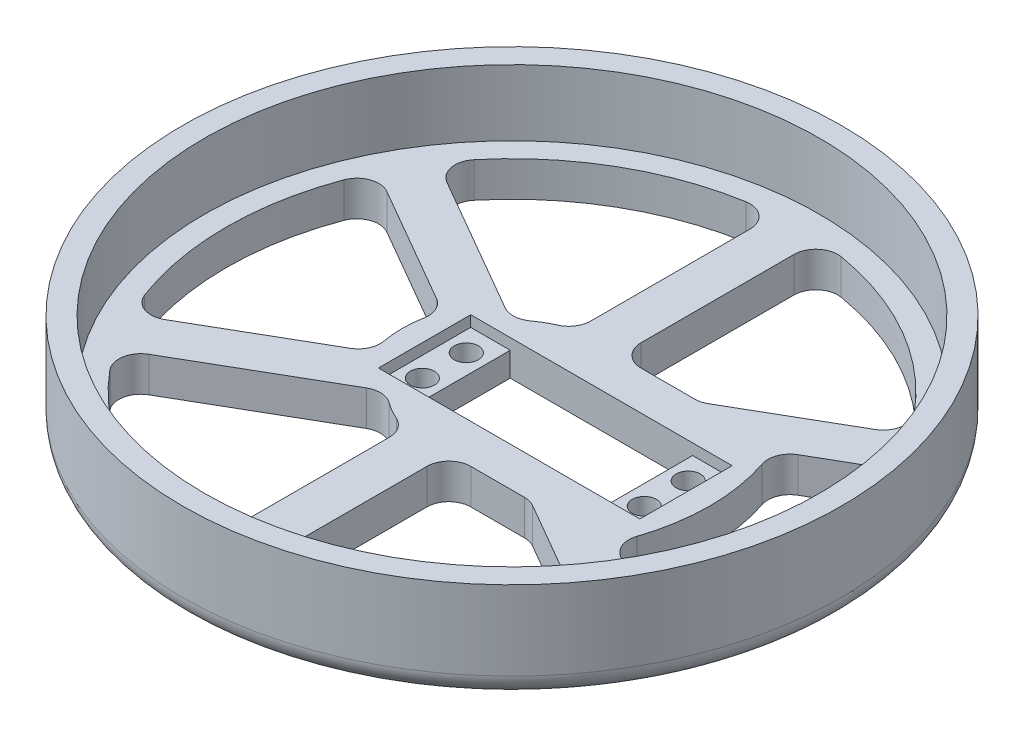
SolidWorks part; units mm, degrees
ref_plane "Front Plane" through (0, 0, 0) normal (0, 0, 1) x (1, 0, 0)
ref_plane "Top Plane" through (0, 0, 0) normal (0, 1, 0) x (1, 0, 0)
ref_plane "Right Plane" through (0, 0, 0) normal (1, 0, 0) x (0, 0, -1)
sketch "Sketch1" plane through (0, 0, 0) normal (0, 1, 0) x (1, 0, 0)
  circle A0 centre (0, 0) radius 75
  dimension "D1" = 150
extrude "Boss-Extrude1" add sketch "Sketch1" along normal blind 8
sketch "Sketch2" plane through (0, 8, 0) normal (0, 1, 0) x (1, 0, 0)
  line L1 (-10.9, 10.5) -> (30.6, 10.5)
  line L2 (-10.9, 10.5) -> (-10.9, -10.5)
  line L3 (-10.9, -10.5) -> (30.6, -10.5)
  line L4 (30.6, 10.5) -> (30.6, -10.5)
  dimension "D1" = 10.9
  dimension "D2" = 41.5
  dimension "D3" = 21
  dimension "D4" = 10.5
sketch "Sketch5" plane through (0, 8, 0) normal (0, 1, 0) x (1, 0, 0)
  circle A0 centre (0, 0) radius 70
  circle A1 centre (0, 0) radius 75
  dimension "D1" = 140
extrude "Boss-Extrude2" add sketch "Sketch5" along normal blind 15
sketch "Sketch6" plane through (0, 0, 0) normal (0, -1, 0) x (1, 0, 0)
  line L0 (5, -19.3649) -> (23.541, -19.3649)
  line L1 (5, 19.3649) -> (23.541, 19.3649)
  line L3 (5, -64.8074) -> (5, -19.3649)
  line L4 (-5, -64.8074) -> (-5, -19.3649)
  line L5 (-53.6249, -36.7338) -> (-14.2705, -14.0126)
  line L6 (-58.6249, -28.0736) -> (-23.7132, -7.9173)
  line L7 (-58.6249, 28.0736) -> (-23.7132, 7.9173)
  line L8 (-53.6249, 36.7338) -> (-14.2705, 14.0126)
  line L9 (-5, 64.8074) -> (-5, 19.3649)
  line L10 (5, 64.8074) -> (5, 19.3649)
  line L11 (53.6249, 36.7338) -> (23.541, 19.3649)
  line L12 (58.6249, 28.0736) -> (41.2298, 18.0306)
  line L13 (58.6249, -28.0736) -> (41.2298, -18.0306)
  line L14 (53.6249, -36.7338) -> (23.541, -19.3649)
  line L15 (41.2298, 18.0306) -> (58.6249, 28.0736)
  line L16 (-14.2705, -14.0126) -> (-53.6249, -36.7338)
  line L17 (5, 19.3649) -> (5, 64.8074)
  line L18 (5, -19.3649) -> (5, -64.8074)
  line L21 (23.541, -19.3649) -> (53.6249, -36.7338)
  line L22 (-5, -19.3649) -> (-5, -64.8074)
  line L23 (-5, 19.3649) -> (-5, 64.8074)
  line L25 (-23.7132, 7.9173) -> (-58.6249, 28.0736)
  line L26 (-14.2705, 14.0126) -> (-53.6249, 36.7338)
  line L27 (41.2298, -18.0306) -> (58.6249, -28.0736)
  line L28 (-23.7132, -7.9173) -> (-58.6249, -28.0736)
  line L29 (23.541, 19.3649) -> (53.6249, 36.7338)
  arc A1 (58.6249, -28.0736) -> (58.6249, 28.0736) centre (0, 0) ccw
  arc A3 (41.2298, -18.0306) -> (41.2298, 18.0306) centre (0, 0) ccw
  arc A5 (-23.7132, 7.9173) -> (-23.7132, -7.9173) centre (0, 0) ccw
  arc A6 (-5, 19.3649) -> (-14.2705, 14.0126) centre (0, 0) ccw
  arc A10 (5, -64.8074) -> (53.6249, -36.7338) centre (0, 0) ccw
  arc A11 (-53.6249, -36.7338) -> (-5, -64.8074) centre (0, 0) ccw
  arc A12 (-58.6249, 28.0736) -> (-58.6249, -28.0736) centre (0, 0) ccw
  arc A13 (-5, 64.8074) -> (-53.6249, 36.7338) centre (0, 0) ccw
  arc A14 (53.6249, 36.7338) -> (5, 64.8074) centre (0, 0) ccw
  arc A17 (-14.2705, -14.0126) -> (-5, -19.3649) centre (0, 0) ccw
  point P35 (0, 0)
  dimension "D2" = 130
  dimension "D3" = 90
  dimension "D6" = 6
extrude "Cut-Extrude6" cut sketch "Sketch2" against normal through all both and the other way through all
sketch "Sketch8" plane through (0, 8, 0) normal (0, 1, 0) x (1, 0, 0)
  line L0 (9.85, 16.633) -> (9.85, -16.695) construction
  line L1 (-10.9, 10.5) -> (-19.9, 10.5)
  line L2 (-10.9, 10.5) -> (-10.9, -10.5)
  line L3 (-10.9, -10.5) -> (-19.9, -10.5)
  line L4 (-19.9, 10.5) -> (-19.9, -10.5)
  line L5 (39.6, 10.5) -> (39.6, -10.5)
  line L6 (30.6, -10.5) -> (39.6, -10.5)
  line L7 (30.6, 10.5) -> (30.6, -10.5)
  line L8 (30.6, 10.5) -> (39.6, 10.5)
  circle A0 centre (-15.4, 5) radius 2.75
  circle A1 centre (-15.4, -5) radius 2.75
  circle A2 centre (35.1, -5) radius 2.75
  circle A3 centre (35.1, 5) radius 2.75
  dimension "D2" = 5.5
  dimension "D3" = 5.5
  dimension "D1" = 9
  dimension "D4" = 10
  dimension "D5" = 5.5
  dimension "D6" = 20.75
  dimension "D7" = 50.5
  dimension "D8" = 50.5
extrude "Cut-Extrude7" cut sketch "Sketch8" against normal blind 2.5
sketch "Sketch9" plane through (0, 8, 0) normal (0, 1, 0) x (1, 0, 0)
  circle A0 centre (-15.4, 5) radius 2.75
  circle A1 centre (-15.4, -5) radius 2.75
  circle A2 centre (35.1, 5) radius 2.75
  circle A3 centre (35.1, -5) radius 2.75
extrude "Cut-Extrude8" cut sketch "Sketch9" against normal through all both and the other way through all
extrude "Cut-Extrude11" cut sketch "Sketch6" against normal through all both and the other way through all contours A3 L13 A1 L12 | L3 A10 L14 L0 | A17 L5 A11 L4 | L7 A12 L6 A5 | L9 A13 L8 A6 | L11 A14 L10 L1 region at (23.37, 0, -40.7131) region at (23.37, 0, 40.7131) region at (-23.1248, 0, -40.0532) region at (-47.3361, 0, 0) region at (-23.1248, 0, 40.0532) region at (54.0019, 0, 0)
fillet "Fillet1" radius 5 24 edges at (53.6249, 4, 36.7338) (5, 4, 64.8074) (-53.6249, 4, 36.7338) (-5, 4, 64.8074) (-58.6249, 4, 28.0736) (-58.6249, 4, -28.0736) (-53.6249, 4, -36.7338) (-5, 4, -64.8074) (5, 4, -64.8074) (53.6249, 4, -36.7338) (58.6249, 4, -28.0736) (58.6249, 4, 28.0736) (41.2298, 4, 18.0306) (41.2298, 4, -18.0306) (5, 4, -19.3649) (23.541, 4, -19.3649) (-14.2705, 4, -14.0126) (-5, 4, -19.3649) (-23.7132, 4, 7.9173) (-23.7132, 4, -7.9173) (-5, 4, 19.3649) (-14.2705, 4, 14.0126) (5, 4, 19.3649) (23.541, 4, 19.3649)
fillet "Fillet2" radius 5 1 edges at (0, 0, 75)
